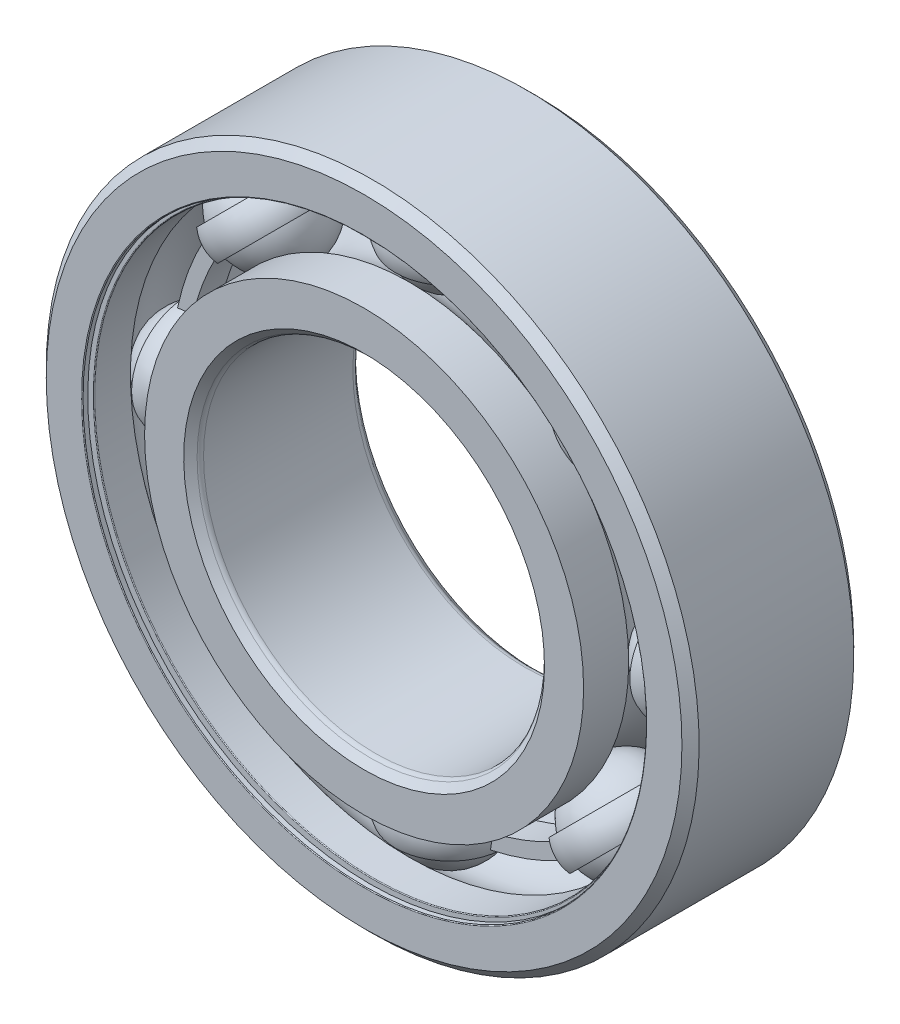
SolidWorks part; units mm, degrees
material "AISI 1020 Steel, Cold Rolled"
ref_plane "Front Plane" through (0, 0, 0) normal (0, 0, 1) x (1, 0, 0)
ref_plane "Top Plane" through (0, 0, 0) normal (0, 1, 0) x (1, 0, 0)
ref_plane "Right Plane" through (0, 0, 0) normal (1, 0, 0) x (0, 0, -1)
sketch "Sketch1" plane through (0, 0, 0) normal (0, 0, 1) x (1, 0, 0)
  line L0 (-9.5, 0) -> (9.5, 0) construction
  line L1 (-5, 0) -> (5, 0) construction
  circle A0 centre (0, 0) radius 5 construction
  circle A1 centre (0, 0) radius 9.5 construction
  point P3 (0, 0)
  point P6 (0, 0)
  point P7 (0, -5)
  point P11 (0, -9.5)
  point P12 (0, 5)
  point P13 (0, 9.5)
  dimension "OD" = 19
  dimension "ID" = 10
sketch "Sketch2" plane through (0, 0, 0) normal (1, 0, 0) x (0, 0, -1)
  line L0 (-2.5, 9.5) -> (2.5, 9.5) construction
  line L1 (0, 9.5) -> (0, -9.5) construction
  line L2 (2.25, 9.5) -> (-2.25, 9.5)
  line L3 (-2.25, 9.5) -> (-2.5, 9.25)
  line L4 (-2.5, 9.25) -> (-2.5, 8.1115)
  line L5 (-2.5, 8.1115) -> (-1.1875, 8.1115)
  line L6 (2.5, 8.1115) -> (1.1875, 8.1115)
  line L7 (2.5, 9.25) -> (2.5, 8.1115)
  line L8 (2.25, 9.5) -> (2.5, 9.25)
  line L9 (0, 9.5) -> (0, 7.25) construction
  line L10 (0, 7.25) -> (0, 5) construction
  line L11 (0, 9.5) -> (0, -9.5) construction
  line L12 (-2.5, 0) -> (2.5, 0) construction
  line L13 (2.5, 5) -> (-2.5, 5) construction
  line L14 (0, 8.7171) -> (0, 5.7829) construction
  line L15 (-2.5, -5) -> (2.5, -5) construction
  line L16 (-2.5, -5) -> (-2.5, 5) construction
  line L17 (2.5, 9.5) -> (2.5, -9.5) construction
  arc A0 (-1.1875, 8.1115) -> (1.1875, 8.1115) centre (0, 7.25) cw
  circle A1 centre (0, 7.25) radius 1.4671 construction
  point P14 (0, 5)
  point P17 (0, 0)
  point P21 (0, 9.5)
  point P29 (0, 5)
  point P30 (0, -5)
  point P35 (0, 8.7171)
  dimension "Approx. Ball Dia." = 2.9342
  dimension "Width" = 5
  dimension "D1" = 45
  dimension "D2" = 0.25
  dimension "D3" = 2.375
  dimension "D4" = 0.8615
  dimension "For Shaft Diameter" = 10
  dimension "For Housing ID" = 19
sketch "Sketch3" plane through (0, 0, 0) normal (1, 0, 0) x (0, 0, -1)
  line L0 (2.25, 9.5) -> (2.5, 9.25) construction
  line L1 (2.5, 9.25) -> (2.5, 8.1115) construction
  line L2 (2.5, 8.1115) -> (1.1875, 8.1115) construction
  line L3 (-2.5, 8.1115) -> (-1.1875, 8.1115) construction
  line L4 (-2.5, 9.25) -> (-2.5, 8.1115) construction
  line L5 (-2.25, 9.5) -> (-2.5, 9.25) construction
  line L6 (2.25, 9.5) -> (-2.25, 9.5) construction
  line L7 (2.25, 9.5) -> (2.5, 9.25)
  line L8 (2.5, 9.25) -> (2.5, 8.1115)
  line L9 (2.5, 8.1115) -> (1.1875, 8.1115)
  line L10 (-2.5, 8.1115) -> (-1.1875, 8.1115)
  line L11 (-2.5, 9.25) -> (-2.5, 8.1115)
  line L12 (-2.25, 9.5) -> (-2.5, 9.25)
  line L13 (2.25, 9.5) -> (-2.25, 9.5)
  arc A0 (1.1875, 8.1115) -> (-1.1875, 8.1115) centre (0, 7.25) ccw construction
  arc A1 (1.1875, 8.1115) -> (-1.1875, 8.1115) centre (0, 7.25) ccw
revolve "Revolve1" add sketch "Sketch3" angle 360 about L12
sketch "Sketch8" plane through (0, 0, 0) normal (1, 0, 0) x (0, 0, -1)
  line L0 (-2.5, 8.1115) -> (-1.1875, 8.1115) construction
  line L1 (-2.34, 8.1115) -> (-2.25, 8.1115)
  line L2 (-2.34, 8.1115) -> (-2.34, 8.5744) construction
  line L3 (-2.34, 8.5744) -> (-2.25, 8.5744)
  line L4 (-2.25, 8.1115) -> (-2.25, 8.5744)
  line L5 (2.5, 8.1115) -> (1.1875, 8.1115) construction
  line L6 (2.25, 8.1115) -> (2.34, 8.1115)
  line L7 (2.25, 8.1115) -> (2.25, 8.5744)
  line L8 (2.25, 8.5744) -> (2.34, 8.5744)
  line L9 (2.34, 8.1115) -> (2.34, 8.5744) construction
  line L10 (-2.25, 8.5744) -> (2.25, 8.5744) construction
  line L11 (0, 9.5) -> (0, -9.5) construction
  line L12 (-2.34, 8.5744) -> (-2.34, 9.0372) construction
  line L13 (-2.34, 9.0372) -> (-2.34, 9.5) construction
  line L14 (-2.5, 9.5) -> (2.5, 9.5) construction
  line L15 (-2.34, 8.1115) -> (-2.5, 8.1115)
  line L16 (-2.5, 8.1115) -> (-2.5, 8.2015)
  line L17 (-2.5, 9.25) -> (-2.5, 8.1115) construction
  line L18 (-2.5, 8.2015) -> (-2.34, 8.2015)
  line L19 (-2.34, 8.2015) -> (-2.34, 8.5744)
  line L20 (2.34, 8.1115) -> (2.5, 8.1115)
  line L21 (2.5, 8.1115) -> (2.5, 8.2015)
  line L22 (2.5, 9.25) -> (2.5, 8.1115) construction
  line L23 (2.5, 8.2015) -> (2.34, 8.2015)
  line L24 (2.34, 8.2015) -> (2.34, 8.5744)
  point P12 (0, 8.5744)
  dimension "D1" = 4.5
  dimension "D2" = 0.09
revolve "Cut-Revolve1" cut sketch "Sketch8" angle 360 about L12
sketch "Sketch4" plane through (0, 0, 0) normal (1, 0, 0) x (0, 0, -1)
  line L0 (0, 9.5) -> (0, -9.5) construction
  line L1 (0, 9.5) -> (0, -9.5) construction
  line L2 (-2.25, 5) -> (-2.5, 5.25)
  line L3 (-2.5, 5.25) -> (-2.5, 6.3885)
  line L5 (-2.5, 6.3885) -> (-1.1875, 6.3885)
  line L6 (-2.25, 5) -> (2.25, 5)
  line L8 (2.25, 5) -> (2.5, 5.25)
  line L10 (2.5, 5.25) -> (2.5, 6.3885)
  line L11 (2.5, 6.3885) -> (1.1875, 6.3885)
  line L12 (-2.5, 9.25) -> (-2.5, 8.1115) construction
  line L13 (2.25, 9.5) -> (2.5, 9.25) construction
  line L15 (2.5, -9.25) -> (2.5, 9.25) construction
  line L16 (2.25, 9.5) -> (2.25, -9.5) construction
  arc A1 (1.1875, 6.3885) -> (-1.1875, 6.3885) centre (0, 7.25) cw
  circle A2 centre (0, 7.25) radius 1.4671 construction
  point P1 (0, 5)
revolve "Revolve2" add sketch "Sketch4" angle 360 about L12
sketch "Sketch5" plane through (0, 0, 0) normal (1, 0, 0) x (0, 0, -1)
  line L0 (-1.4671, 7.25) -> (1.4671, 7.25)
  arc A2 (-1.4671, 7.25) -> (1.4671, 7.25) centre (0, 7.25) cw
  arc A3 (1.1875, 8.1115) -> (-1.1875, 8.1115) centre (0, 7.25) ccw construction
revolve "Revolve3" add sketch "Sketch5" angle 360 about L0
sketch "Sketch6" plane through (0, 0, 0) normal (1, 0, 0) x (0, 0, -1)
  line L0 (-1.1875, 8.1115) -> (-1.1875, 7.6808) construction
  line L1 (-1.1875, 7.6808) -> (-1.1875, 7.25) construction
  line L2 (-1.1875, 7.25) -> (-1.1875, 6.8192) construction
  line L3 (-1.1875, 6.8192) -> (-1.1875, 6.3885) construction
  line L4 (-2.5, 7.6808) -> (-2.3171, 7.6808) construction
  line L5 (-1.1875, 7.6808) -> (-1.1875, 6.8192) construction
  line L7 (-2.3171, 7.6808) -> (-2.1341, 7.6808) construction
  line L8 (-2.1341, 7.6808) -> (-1.9512, 7.6808) construction
  line L10 (0, 9.5) -> (0, -9.5) construction
  line L11 (0, 9.5) -> (0, -9.5) construction
  line L12 (-2.5, 8.1115) -> (-2.5, 7.6808) construction
  line L13 (-1.5854, 7.6808) -> (-1.4024, 7.6808) construction
  line L14 (-2.5, 9.25) -> (-2.5, -9.25) construction
  line L15 (-2.5, 7.6808) -> (-2.5, 7.25) construction
  line L16 (-2.5, 7.25) -> (-2.5, 6.8192) construction
  line L17 (-2.5, 6.8192) -> (-2.5, 6.3885) construction
  line L18 (-1.9512, 7.6808) -> (-1.7683, 7.6808) construction
  line L19 (-1.7683, 7.6808) -> (-1.5854, 7.6808) construction
  line L20 (-1.4024, 7.6808) -> (-1.5854, 7.6808)
  line L21 (-2.5, 6.8192) -> (-2.3171, 6.8192) construction
  line L22 (-2.3171, 6.8192) -> (-2.1341, 6.8192) construction
  line L23 (-2.1341, 6.8192) -> (-1.9512, 6.8192) construction
  line L24 (-1.9512, 6.8192) -> (-1.7683, 6.8192) construction
  line L25 (-1.7683, 6.8192) -> (-1.5854, 6.8192) construction
  line L26 (-1.5854, 6.8192) -> (-1.4024, 6.8192) construction
  line L27 (-1.4024, 6.8192) -> (-1.5854, 6.8192)
  line L28 (-1.7683, 7.6808) -> (-1.7683, 6.8192) construction
  line L30 (-1.6768, 7.6808) -> (-1.6768, 6.8192) construction
  circle A0 centre (0, 7.25) radius 1.4671 construction
  arc A2 (-1.5854, 6.8192) -> (-1.5854, 7.6808) centre (-0.6167, 7.25) cw
  arc A3 (-1.4024, 7.6808) -> (-1.4024, 6.8192) centre (0, 7.25) ccw
revolve "Revolve4" add sketch "Sketch6" angle 360 about L11
sketch "Sketch7" plane through (0, 0, 0) normal (0, 0, 1) x (1, 0, 0)
  line L0 (-1.4671, 7.25) -> (1.4671, 7.25) construction
  line L1 (0, 5.7829) -> (0, 8.7171) construction
  line L2 (0, 0) -> (2.7745, 6.6981) construction
  line L8 (0, 9.5) -> (0, -9.5) construction
  line L9 (5.1265, 5.1265) -> (5.4311, 5.4311)
  line L10 (0, 9.5) -> (0, -9.5) construction
  line L11 (0, 7.6808) -> (0, 7.25)
  arc A1 (5.1265, 5.1265) -> (0, 7.25) centre (0, 0) ccw
  arc A2 (5.4311, 5.4311) -> (0, 7.6808) centre (0, 0) ccw
  dimension "D1" = 45
  dimension "D2" = 2.9342
extrude "Boss-Extrude1" add sketch "Sketch7" along normal mid plane 0.8333
pattern_circular "CirPattern1" count 8 over 360 about axis through (0, 0, 2.5) along (0, 0, -1) of bodies 104 134
pattern_circular "CirPattern2" count 8 over 360 about axis through (0, 0, 2.5) along (0, 0, -1) of "Revolve4", "Boss-Extrude1" reverse direction yes
fillet "Fillet1" radius 0.0225 4 edges at (0, -8.1115, -2.25) (0, -8.2015, -2.5) (0, -8.1115, 2.25) (0, -8.2015, 2.5)
fillet "Fillet2" radius 0.1875 2 edges at (0, -5, -2.25) (0, -5, 2.25)
ref_plane "Plane1" through (2.7745, 6.6981, 0) normal (0.3827, 0.9239, 0) x (0.9239, -0.3827, 0)
sketch "Sketch9" plane through (2.7745, 6.6981, 0) normal (0.3827, 0.9239, 0) x (0.9239, -0.3827, 0)
  line L0 (-1.419, -0.4167) -> (-1.419, -1.25)
  line L1 (-1.419, -1.25) -> (-0.6155, -1.25)
  line L2 (-0.6155, -1.25) -> (0, -0.7335)
  line L3 (0, -0.7335) -> (0.6155, -1.25)
  line L4 (0.6155, -1.25) -> (1.419, -1.25)
  line L5 (1.419, -1.25) -> (1.419, -0.4167)
  line L6 (1.419, -0.4167) -> (-1.419, -0.4167)
  line L7 (0, -0.4167) -> (0, 0) construction
  line L8 (-1.419, -0.4167) -> (-1.419, 0) construction
  dimension "D1" = 0.8333
  dimension "D2" = 0.4167
  dimension "D3" = 40
extrude "Boss-Extrude2" [suppressed] add sketch "Sketch9" along normal blind 1.2837 draft 15 and the other way blind 1.2837 draft 10 separate body draft outward yes other way draft outward yes
fillet "Fillet3" [suppressed] radius 0.25
mirror "Mirror1" [suppressed] about plane through (0, 0, 0) normal (0, 0, 1) of bodies 149
pattern_circular "CirPattern3" [suppressed] count 8 over 360 about axis through (0, 0, 2.5) along (0, 0, -1) of bodies 158 149
equation "\"D2@Sketch2\" = \"Width@Sketch2\" * .05"
equation "\"D3@Sketch2\"=\"Width@Sketch2\" * .475"
equation "\"D4@Sketch2\" =  (  (  ( \"OD@Sketch1\" - \"Width@Sketch2\" )  / 2 )  / 3.25 )  / 2.5"
equation "\"D1@Boss-Extrude1\" = \"Width@Sketch2\" / 6"
equation "\"D1@Sketch8\"=\"Width@Sketch2\"*.9"
equation "\"D2@Sketch8\"=\"D1@Sketch8\"*.02"
equation "\"D1@Fillet1\" = \"D2@Sketch8\" * .25"
equation "\"D1@Fillet2\" = \"D2@Sketch2\" * .75"
equation "\"Approx No of Balls@CirPattern1\" = ( pi * \"OD@Sketch1\" ) * .4 / \"Approx. Ball Dia.@Sketch2\""
equation "\"D1@Sketch7\" = 360 / \"Approx No of Balls@CirPattern1\""
equation "\"D1@CirPattern2\" = \"Approx No of Balls@CirPattern1\""
equation "\"D2@Sketch7\"=\"Approx. Ball Dia.@Sketch2\""
equation "\"D2@Sketch9\" = \"D1@Boss-Extrude1\" * .5"
equation "\"D1@Sketch9\"=\"D2@Sketch9\"*2"
equation "\"D1@Boss-Extrude2\"=\"Approx. Ball Dia.@Sketch2\"*.4375"
equation "\"D2@Boss-Extrude2\"=\"D1@Boss-Extrude2\""
equation "\"D1@CirPattern3\" = \"Approx No of Balls@CirPattern1\""
equation "\"D1@Fillet3\"=\"D1@Sketch9\" * .3"
